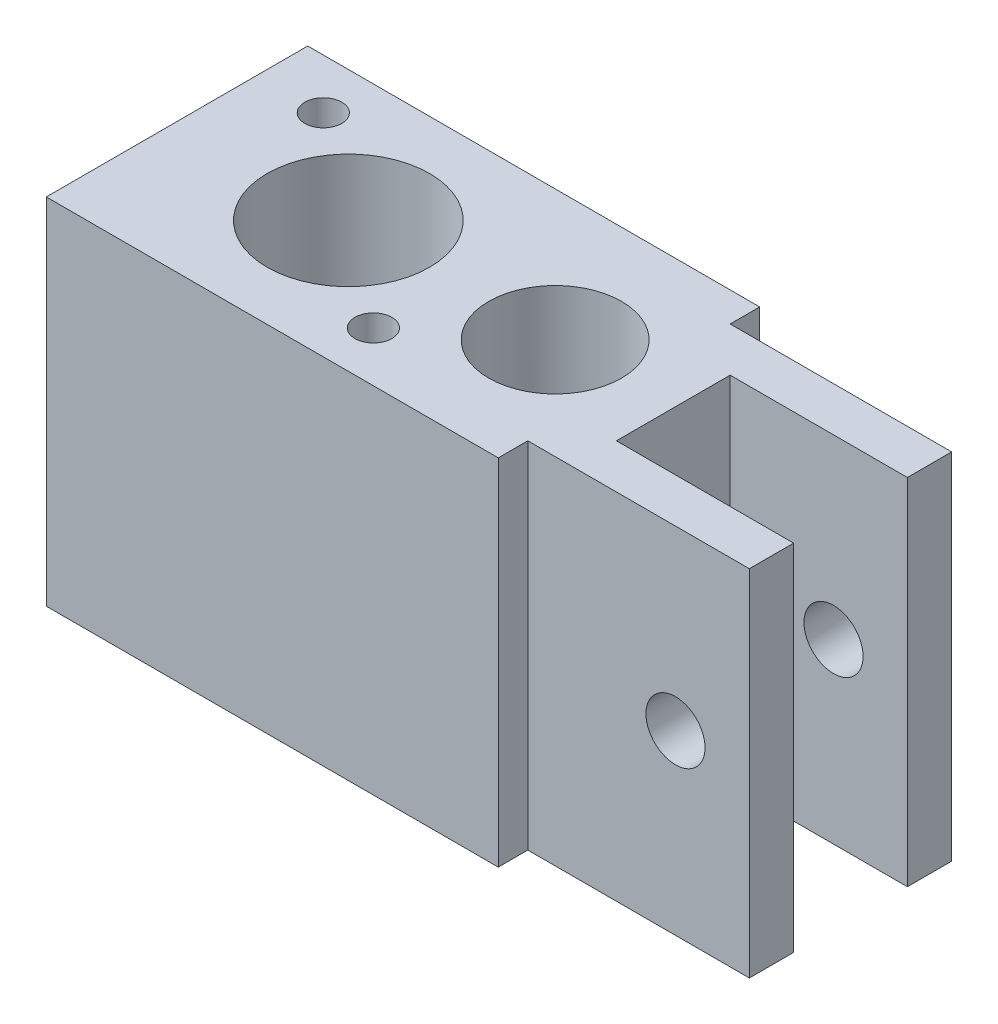
SolidWorks part; units mm, degrees
ref_plane "Ebene vorne" through (0, 0, 0) normal (0, 0, 1) x (1, 0, 0)
ref_plane "Ebene oben" through (0, 0, 0) normal (0, 1, 0) x (1, 0, 0)
ref_plane "Ebene rechts" through (0, 0, 0) normal (1, 0, 0) x (0, 0, -1)
sketch "Skizze1" plane through (0, 0, 0) normal (0, 0, 1) x (1, 0, 0)
  line L1 (-11.6, 588.1) -> (34, 588.1)
  line L2 (-11.6, 588.1) -> (-11.6, 564.1)
  line L3 (-11.6, 564.1) -> (34, 564.1)
  line L4 (34, 588.1) -> (34, 564.1)
  circle A0 centre (29, 576.1) radius 2
  point P6 (-11.6, 576.1)
sketch "Skizze2" plane through (0, 0, 0) normal (0, 1, 0) x (1, 0, 0)
  line L1 (-12.6, 8.85) -> (19, 8.85)
  line L2 (-12.6, 8.85) -> (-12.6, -8.85)
  line L3 (-12.6, 0) -> (22, 0)
  line L4 (34, 6.85) -> (34, 3.85)
  line L8 (34, 6.85) -> (19, 6.85)
  line L9 (19, 8.85) -> (19, 6.85)
  line L10 (19, -8.85) -> (19, -6.85)
  line L11 (34, -6.85) -> (19, -6.85)
  line L12 (-12.6, -8.85) -> (19, -8.85)
  line L13 (34, -3.85) -> (22, -3.85)
  line L14 (34, 3.85) -> (22, 3.85)
  line L17 (22, 3.85) -> (22, -3.85)
  line L18 (34, -3.85) -> (34, -6.85)
  circle A0 centre (14, 0) radius 4.5
  circle A1 centre (0, 0) radius 5.5
sketch "Skizze3" plane through (0, 0, 0) normal (0, 1, 0) x (1, 0, 0)
  line L0 (-12.6, -8.85) -> (-12.6, 8.85)
  line L1 (-12.6, 8.85) -> (19, 8.85)
  line L2 (19, 8.85) -> (19, 6.85)
  line L3 (19, 6.85) -> (34, 6.85)
  line L5 (-132.3655, 0) -> (132.3655, 0) construction
  line L6 (19, -6.85) -> (34, -6.85)
  line L7 (19, -8.85) -> (19, -6.85)
  line L8 (-12.6, -8.85) -> (19, -8.85)
  line L9 (34, 6.85) -> (34, 3.85)
  line L10 (22, -3.85) -> (22, 3.85)
  line L11 (22, 3.85) -> (34, 3.85)
  line L12 (-25.63, 0) -> (25.63, 0) construction
  line L13 (34, -6.85) -> (34, -3.85)
  line L14 (22, -3.85) -> (34, -3.85)
  circle A0 centre (0, 0) radius 5.5
  circle A1 centre (14, 0) radius 4.5
  point P21 (34, 0)
  point P24 (-12.6, 0)
  point P34 (22, 0)
sketch "Skizze5" plane through (0, 0, 0) normal (0, 0, 1) x (1, 0, 0)
  line L1 (-11.6, 588.1) -> (34, 588.1)
  line L2 (-11.6, 588.1) -> (-11.6, 564.1)
  line L3 (-11.6, 564.1) -> (34, 564.1)
  line L4 (34, 588.1) -> (34, 564.1)
  circle A0 centre (29, 576.1) radius 2
extrude "Aufsatz-Linear austragen1" add sketch "Skizze3" along normal up to vertex (588.1 mm away) up to point (34, 588.1, 0)
extrude "Schnitt-Linear austragen2" cut sketch "Skizze5" against normal through all both and the other way through all flip side to cut
sketch "Sketch2" plane through (0, 588.1, 0) normal (0, 1, 0) x (1, 0, 0)
  line L0 (-11.6, 8.85) -> (11.6, -8.85) construction
  line L1 (-12.6, -8.85) -> (19, -8.85) construction
  circle A0 centre (0, 0) radius 9
  circle A1 centre (-7.1553, 5.459) radius 1.25
  circle A2 centre (7.1553, -5.459) radius 1.25
  point P13 (-8.2363, 4.8313)
extrude "Cut-Extrude1" cut sketch "Sketch2" against normal blind 6 contours A2 | A1
